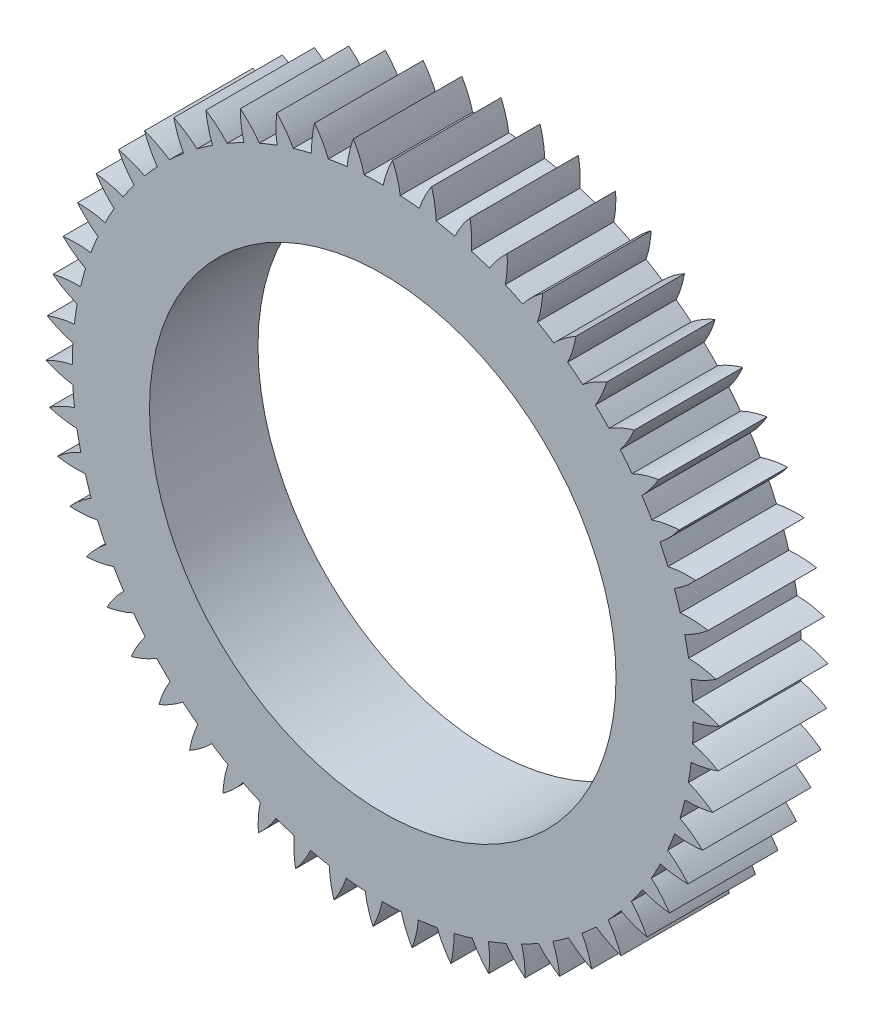
SolidWorks part; units mm, degrees
ref_plane "Front Plane" through (0, 0, 0) normal (0, 0, 1) x (1, 0, 0)
ref_plane "Top Plane" through (0, 0, 0) normal (0, 1, 0) x (1, 0, 0)
ref_plane "Right Plane" through (0, 0, 0) normal (1, 0, 0) x (0, 0, -1)
sketch "Sketch1" plane through (0, 0, 0) normal (0, 0, 1) x (1, 0, 0)
  line L0 (0, 0) -> (62.1959, -1.8097) construction
  line L1 (0, 0) -> (62.1959, 1.8097) construction
  line L2 (0, 0) -> (62.1959, -1.8097) construction
  line L3 (0, 0) -> (62.2222, 0) construction
  line L4 (0, 0) -> (61.9854, 5.423) construction
  line L6 (62.1959, 1.8097) -> (42.9818, 1.2506)
  line L7 (57.198, -1.6643) -> (42.9818, -1.2506)
  circle A0 centre (0, 0) radius 60 construction
  circle A1 centre (0, 0) radius 57.2222 construction
  circle A2 centre (0, 0) radius 56.3816 construction
  circle A3 centre (0, 0) radius 62.2222 construction
  arc A4 (57.2175, 0.7341) -> (57.198, -1.6643) centre (0, 0) cw
  arc A5 (42.9818, -1.2506) -> (42.9818, 1.2506) centre (0, 0) ccw
  arc A6 (62.1941, 1.8705) -> (62.1959, 1.8097) centre (0, 0) ccw
  spline S0 degree 4 poles (56.3816, 0) (56.4651, 0.0025) (56.699, 0.0173) (57.1389, 0.0757) (57.85, 0.214) (58.7435, 0.4527) (59.8791, 0.832) (61.1875, 1.368) (62.5891, 2.0488) (64.069, 2.8851) (65.5016, 3.8027) (66.8858, 4.7917) (68.2223, 5.8442) (69.7865, 7.1909) (71.585, 8.913) (73.5628, 11.056) (75.6559, 13.6606) (77.611, 16.4463) (79.3928, 19.3457) (80.8034, 21.9677) (81.9089, 24.2676) (82.762, 26.2144) (83.4043, 27.79) (84.0064, 29.379) (84.5697, 30.9865) (85.0928, 32.6001) (85.5792, 34.2375) (86.0244, 35.8662) (86.4369, 37.5373) (86.8035, 39.1614) (87.1061, 40.6795) (87.3201, 41.8405) (87.5125, 42.9995) (87.6079, 43.6062) (87.7326, 44.4454) (87.8218, 45.0963) (87.9167, 45.8228) (87.999, 46.5085) (88.0792, 47.2198) (88.1508, 47.9156) (88.2015, 48.4472) (88.2325, 48.7971) (88.2478, 48.9732) knots 0 0 0 0 0 0.005377 0.015084 0.028532 0.04661 0.064855 0.092111 0.119476 0.146842 0.174209 0.201575 0.228941 0.256307 0.307035 0.361767 0.4165 0.471232 0.525964 0.580697 0.608063 0.635429 0.662795 0.690161 0.717528 0.744894 0.77226 0.799626 0.826992 0.854358 0.881725 0.895408 0.909091 0.920455 0.931818 0.943182 0.954545 0.965909 0.977273 0.988636 1 1 1 1 1 construction
  spline S1 degree 4 poles (56.3816, 0) (56.4651, 0.0025) (56.699, 0.0173) (57.1389, 0.0757) (57.85, 0.214) (58.7435, 0.4527) (59.8791, 0.832) (61.1875, 1.368) (62.5891, 2.0488) (64.069, 2.8851) (65.5016, 3.8027) (66.8858, 4.7917) (68.2223, 5.8442) (69.7865, 7.1909) (71.585, 8.913) (73.5628, 11.056) (75.6559, 13.6606) (77.611, 16.4463) (79.3928, 19.3457) (80.8034, 21.9677) (81.9089, 24.2676) (82.762, 26.2144) (83.4043, 27.79) (84.0064, 29.379) (84.5697, 30.9865) (85.0928, 32.6001) (85.5792, 34.2375) (86.0244, 35.8662) (86.4369, 37.5373) (86.8035, 39.1614) (87.1061, 40.6795) (87.3201, 41.8405) (87.4794, 42.8002) (87.5396, 43.1752) (87.5695, 43.3661) knots 0 0 0 0 0 0.005377 0.015084 0.028532 0.04661 0.064855 0.092111 0.119476 0.146842 0.174209 0.201575 0.228941 0.256307 0.307035 0.361767 0.4165 0.471232 0.525964 0.580697 0.608063 0.635429 0.662795 0.690161 0.717528 0.744894 0.77226 0.799626 0.826992 0.854358 0.881725 0.895408 0.909091 0.909091 0.909091 0.909091 0.909091
  point P6 (56.3816, 0)
  dimension "pitchRadius" = 60
  dimension "addendumRadius" = 62.2222
  dimension "dedendumRadius" = 57.2222
  dimension "baseRadius" = 56.3816
  dimension "D1" = 3.333
  dimension "D2" = 1.667
  dimension "toothArc" = 6.667
  dimension "D3" = 43
extrude "Boss-Extrude1" add sketch "Sketch1" along normal blind 20 contours S1 region at (51.2583, 0.1102, 0)
mirror "Mirror1" about plane through (0, 0, 20) normal (0.0291, -0.9996, 0) of "Boss-Extrude1"
pattern_circular "CirPattern2" count 54 over 360 about axis through (0, 0, 20) along (0, 0, -1) of "Boss-Extrude1", "Mirror1"
equation "\"D2@Sketch1\"=\"toothArc@Sketch1\"/4"
equation "\"pitchRadius\"= 6"
equation "\"nTeeth\"= 54"
equation "\"pressureAngle\"= 20"
equation "\"baseRadius\"= \"pitchRadius\" * cos ( \"pressureAngle\" )"
equation "\"diametralPitch\"= \"nTeeth\" / ( 2 * \"pitchRadius\" )'note units: cm^-1"
equation "\"dedendum\"= 1.25 / \"diametralPitch\"'for full depth, 20 deg pressure angle"
equation "\"addendum\"= 1 / \"diametralPitch\""
equation "\"pitchRadius@Sketch1\"= \"pitchRadius\""
equation "\"addendumRadius@Sketch1\"= \"pitchRadius\" + \"addendum\""
equation "\"dedendumRadius@Sketch1\"= \"pitchRadius\" - \"dedendum\""
equation "\"baseRadius@Sketch1\"= \"baseRadius\""
equation "\"toothArc@Sketch1\"=360/\"nTeeth\""
equation "\"D2@CirPattern2\"=\"nTeeth\""
equation "\"D1@CirPattern2\"= \"nTeeth\""
equation "\"D1@Sketch1\"=\"toothArc@Sketch1\"/2"
